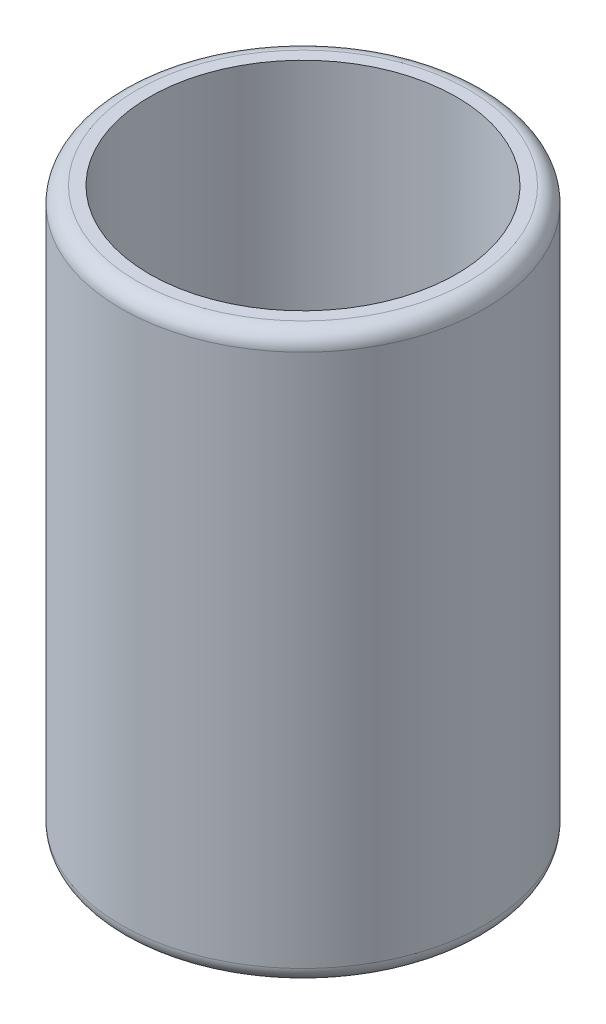
SolidWorks part; units mm, degrees
ref_plane "Front Plane" through (0, 0, 0) normal (0, 0, 1) x (1, 0, 0)
ref_plane "Top Plane" through (0, 0, 0) normal (0, 1, 0) x (1, 0, 0)
ref_plane "Right Plane" through (0, 0, 0) normal (1, 0, 0) x (0, 0, -1)
sketch "Sketch1" plane through (0, 0, 0) normal (0, 1, 0) x (1, 0, 0)
  circle A0 centre (0, 0) radius 57.15
  circle A1 centre (0, 0) radius 48.26
  dimension "D1" = 114.3
  dimension "D2" = 96.52
  dimension "T" = 8.89
extrude "Boss-Extrude1" add sketch "Sketch1" along normal blind 8.89 contours A1 | A0 A1 region at (-55.5336, 0, 0) region at (0, 0, 0)
extrude "Boss-Extrude2" add sketch "Sketch1<4>" along normal blind 177.8
sketch "Sketch1<4>" plane through (0, 0, 0) normal (0, 1, 0) x (1, 0, 0) same geometry as "Sketch1"
fillet "Fillet1" radius 5 2 edges at (0, 0, 57.15) (0, 177.8, 57.15)
equation "\"OD\"=114.3"
equation "\"D1@Sketch1\"=\"OD\""
equation "\"ID\"=96.52"
equation "\"D2@Sketch1\"=\"ID\""
equation "\"D1@Boss-Extrude1\"=0.5*(\"OD\"-\"ID\")"
equation "\"H\"=177.8"
equation "\"D1@Boss-Extrude2\"=\"H\""
